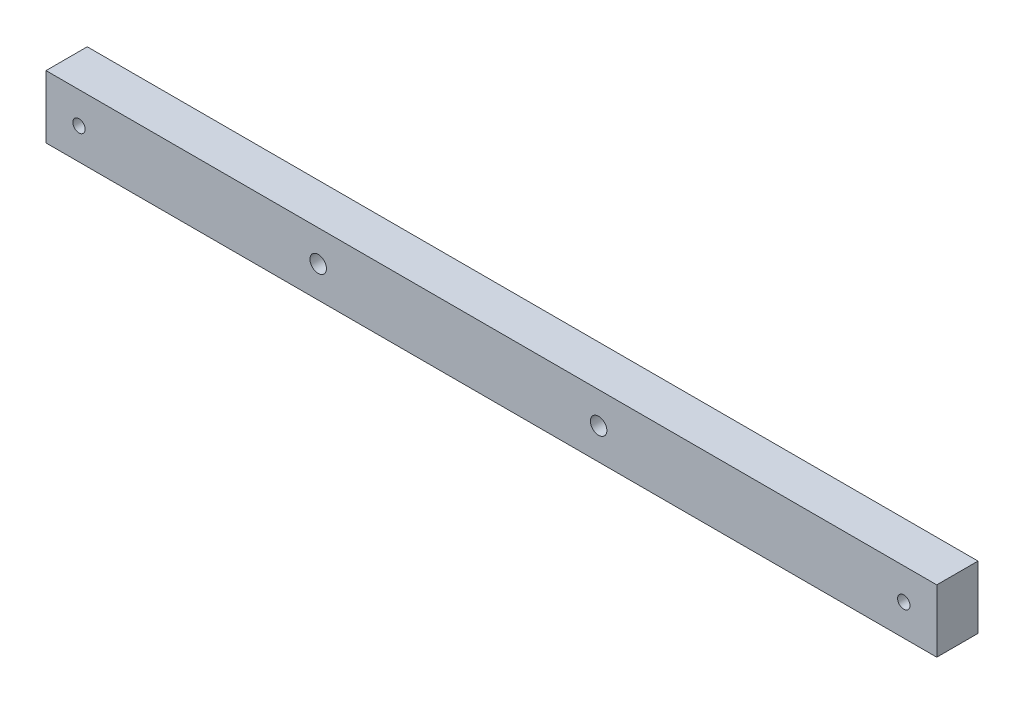
SolidWorks part; units mm, degrees
ref_plane "前视基准面" through (0, 0, 0) normal (0, 0, 1) x (1, 0, 0)
ref_plane "上视基准面" through (0, 0, 0) normal (0, 1, 0) x (1, 0, 0)
ref_plane "右视基准面" through (0, 0, 0) normal (1, 0, 0) x (0, 0, -1)
sketch "草图2" plane through (0, 0, 0) normal (0, 0, 1) x (1, 0, 0)
  line L0 (0, 0) -> (0, -11.1015) construction
  line L1 (-27, 1.9) -> (27, 1.9)
  line L2 (-27, 1.9) -> (-27, -1.9)
  line L3 (-27, -1.9) -> (27, -1.9)
  line L4 (27, 1.9) -> (27, -1.9)
  line L5 (-27, 1.9) -> (27, -1.9) construction
  line L6 (-27, -1.9) -> (27, 1.9) construction
  circle A1 centre (6.5, 0) radius 0.5
  circle A3 centre (-10.5, 0) radius 0.5
  point P0 (0, 0)
  dimension "D3" = 1
  dimension "D5" = 1
  dimension "D4" = 17
  dimension "D1" = 3.8
  dimension "D2" = 54
  dimension "D6" = 16.5
extrude "凸台-拉伸1" add sketch "草图2" along normal blind 2.5
sketch "草图3" plane through (0, 0, 0) normal (0, 0, -1) x (-1, 0, 0)
  line L0 (27, 1.9) -> (27, -1.9) construction
  line L1 (27, -1.9) -> (-27, -1.9) construction
  line L2 (-27, 1.9) -> (27, 1.9) construction
  line L3 (25, -1.9) -> (25, 1.9) construction
  line L4 (-27, 0) -> (-25, 0) construction
  line L5 (-27, -1.9) -> (-27, 1.9) construction
  circle A0 centre (25, 0) radius 0.375
  circle A1 centre (-25, 0) radius 0.375
  dimension "D1" = 0.75
  dimension "D3" = 0.75
  dimension "D2" = 2
  dimension "D4" = 2
extrude "切除-拉伸1" cut sketch "草图3" against normal up to next
